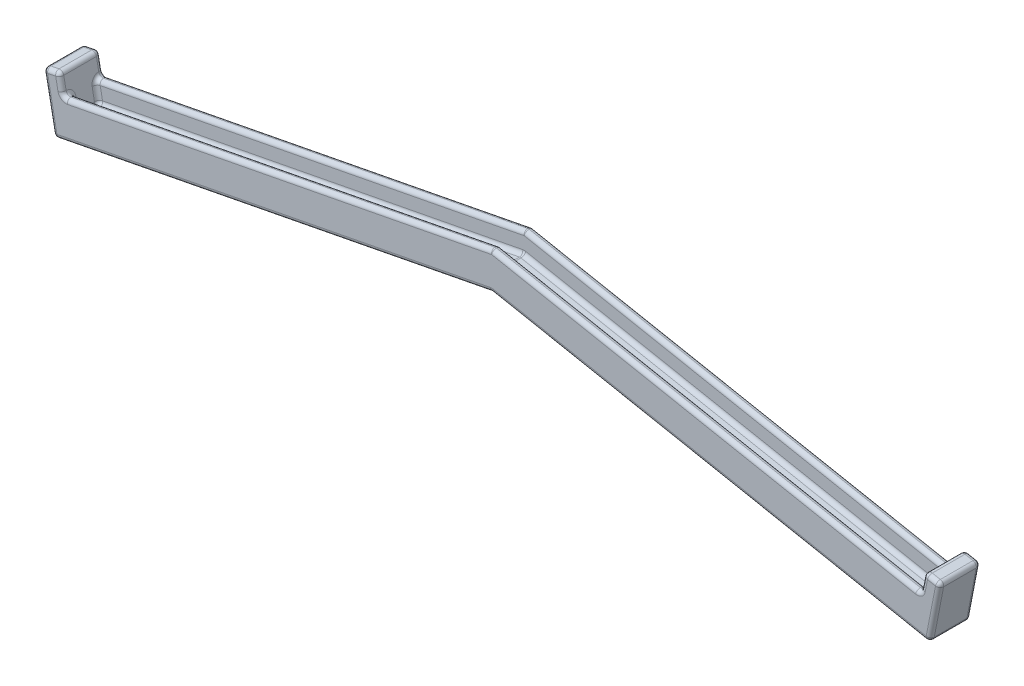
SolidWorks part; units mm, degrees
ref_plane "Płaszczyzna przednia" through (0, 0, 0) normal (0, 0, 1) x (1, 0, 0)
ref_plane "Płaszczyzna górna" through (0, 0, 0) normal (0, 1, 0) x (1, 0, 0)
ref_plane "Płaszczyzna prawa" through (0, 0, 0) normal (1, 0, 0) x (0, 0, -1)
sketch "Szkic1" plane through (0, 0, 0) normal (0, 0, 1) x (1, 0, 0)
  line L0 (0, 0) -> (1080, 0) construction
  line L1 (1060.3636, 3.7965) -> (540, 104.4031)
  line L2 (540, 104.4031) -> (19.6364, 3.7965)
  line L3 (0, 0) -> (-9.4912, 49.0909)
  line L4 (-9.4912, 49.0909) -> (10.1452, 52.8874)
  line L5 (10.1452, 52.8874) -> (19.6364, 3.7965)
  line L6 (1080, 0) -> (1089.4912, 49.0909)
  line L7 (1089.4912, 49.0909) -> (1069.8548, 52.8874)
  line L8 (1069.8548, 52.8874) -> (1060.3636, 3.7965)
  line L9 (1080, 0) -> (1076.2035, -19.6364)
  line L10 (0, 0) -> (3.7965, -19.6364)
  line L11 (540, 104.4031) -> (540, 84.4031) construction
  line L12 (1080, 0) -> (1080.4444, 1.256)
  line L13 (3.7965, -19.6364) -> (540, 84.4031)
  line L14 (540, 84.4031) -> (1076.2035, -19.6364)
  dimension "D1" = 550
  dimension "D2" = 550
  dimension "D3" = 1080
  dimension "D4" = 90
  dimension "D5" = 50
  dimension "D6" = 20
  dimension "D7" = 90
  dimension "D8" = 50
  dimension "D9" = 20
  dimension "D10" = 90
  dimension "D11" = 20
  dimension "D12" = 20
  dimension "D13" = 20
  dimension "D14" = 546.2036
  dimension "D15" = 530
  dimension "D16" = 530
extrude "Dodanie-wyciągnięcie1" add sketch "Szkic1" along normal blind 50 contours L6 L7 L8 L1 L2 L5 L4 L3 L10 L13 L14 L9
sketch "Szkic4" plane through (0, 0, 50) normal (0, 0, 1) x (1, 0, 0)
  line L0 (19.6364, 3.7965) -> (14.8908, 28.3419)
  line L1 (10.1452, 52.8874) -> (19.6364, 3.7965) construction
  line L2 (14.8908, 28.3419) -> (540, 129.866)
  line L3 (540, 129.866) -> (1065.1092, 28.3419)
  line L4 (1069.8548, 52.8874) -> (1060.3636, 3.7965) construction
  line L5 (1065.1092, 28.3419) -> (1060.3636, 3.7965)
  line L6 (1060.3636, 3.7965) -> (540, 104.4031)
  line L7 (540, 104.4031) -> (19.6364, 3.7965)
extrude "Dodanie-wyciągnięcie4" add sketch "Szkic4" against normal blind 10
sketch "Szkic5" plane through (0, 0, 0) normal (0, 0, -1) x (-1, 0, 0)
  line L0 (-1060.3636, 3.7965) -> (-1065.1092, 28.3419)
  line L1 (-1069.8548, 52.8874) -> (-1060.3636, 3.7965) construction
  line L2 (-1065.1092, 28.3419) -> (-540, 129.866)
  line L3 (-540, 129.866) -> (-14.8908, 28.3419)
  line L4 (-14.8908, 28.3419) -> (-19.6364, 3.7965)
  line L5 (-10.1452, 52.8874) -> (-19.6364, 3.7965) construction
  line L6 (-540, 104.4031) -> (-19.6364, 3.7965) construction
  line L7 (-19.6364, 3.7965) -> (-540, 104.4031)
  line L8 (-540, 104.4031) -> (-1060.3636, 3.7965)
extrude "Dodanie-wyciągnięcie5" add sketch "Szkic5" against normal blind 10
fillet "Zaokrąglenie1" radius 5 42 edges at (540, 84.4031, 25) (3.7965, -19.6364, 25) (-9.4912, 49.0909, 25) (10.1452, 52.8874, 25) (19.6364, 3.7965, 25) (540, 104.4031, 25) (1076.2035, -19.6364, 25) (1089.4912, 49.0909, 25) (1069.8548, 52.8874, 25) (1060.3636, 3.7965, 25) (279.8182, 54.0998, 10) (17.2636, 16.0692, 10) (277.4454, 79.104, 10) (802.5546, 79.104, 10) (1062.7364, 16.0692, 10) (800.1818, 54.0998, 10) (800.1818, 54.0998, 40) (1062.7364, 16.0692, 40) (802.5546, 79.104, 40) (277.4454, 79.104, 40) (17.2636, 16.0692, 40) (279.8182, 54.0998, 40) (1079.673, 50.9891, 50) (1082.8474, 14.7273, 50) (808.1018, 32.3834, 50) (271.8982, 32.3834, 50) (-2.8474, 14.7273, 50) (0.327, 50.9891, 50) (12.518, 40.6147, 50) (277.4454, 79.104, 50) (802.5546, 79.104, 50) (1067.482, 40.6147, 50) (0.327, 50.9891, 0) (-2.8474, 14.7273, 0) (271.8982, 32.3834, 0) (808.1018, 32.3834, 0) (1082.8474, 14.7273, 0) (1079.673, 50.9891, 0) (1067.482, 40.6147, 0) (802.5546, 79.104, 0) (277.4454, 79.104, 0) (12.518, 40.6147, 0)
